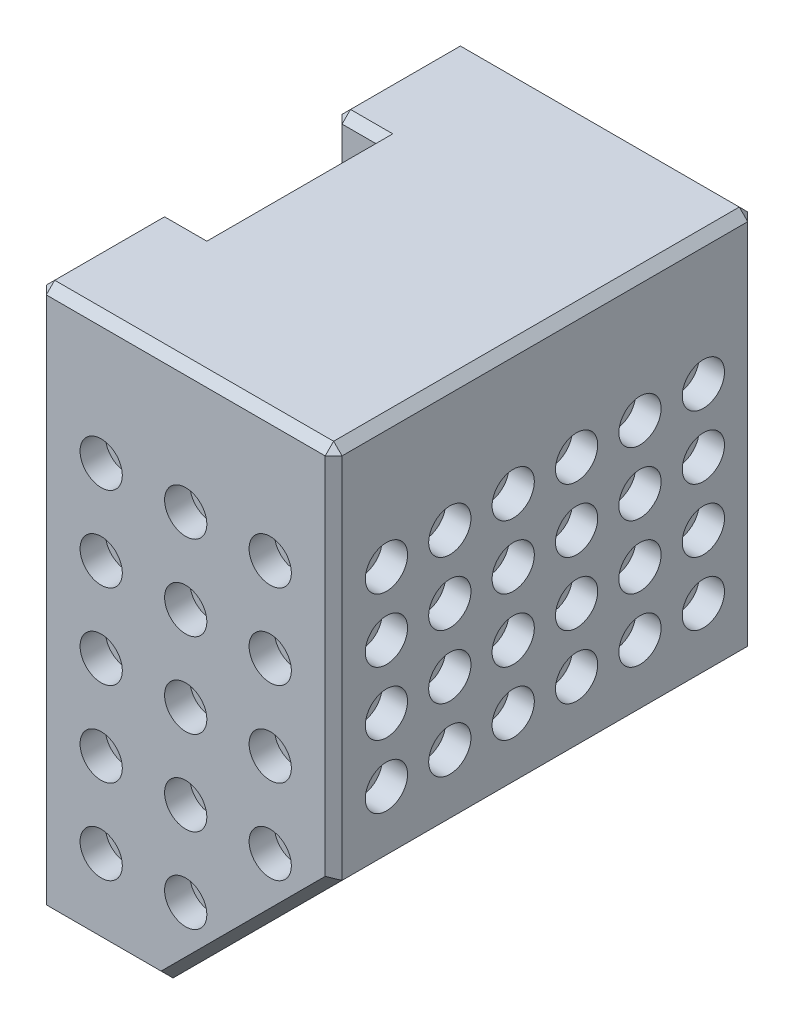
SolidWorks part; units mm, degrees
material "K110"
ref_plane "Front Plane" through (0, 0, 0) normal (0, 0, 1) x (1, 0, 0)
ref_plane "Top Plane" through (0, 0, 0) normal (0, 1, 0) x (1, 0, 0)
ref_plane "Right Plane" through (0, 0, 0) normal (1, 0, 0) x (0, 0, -1)
sketch "Sketch1" plane through (0, 0, 0) normal (0, 1, 0) x (1, 0, 0)
  line L1 (-17.5, -25) -> (17.5, -25)
  line L2 (-17.5, -25) -> (-17.5, 25)
  line L3 (-17.5, 25) -> (17.5, 25)
  line L4 (17.5, -25) -> (17.5, 25)
  line L5 (-17.5, -25) -> (17.5, 25) construction
  line L6 (-17.5, 25) -> (17.5, -25) construction
  point P0 (0, 0)
  dimension "D1" = 50
  dimension "D2" = 35
extrude "Boss-Extrude1" add sketch "Sketch1" against normal blind 64.5
sketch "Sketch2" plane through (0, 0, 25) normal (0, 0, 1) x (1, 0, 0)
  line L0 (-2.5, -64.5) -> (17.5, -44.5)
  line L1 (-17.5, -64.5) -> (17.5, -64.5) construction
  line L2 (17.5, -64.5) -> (17.5, 0) construction
  line L3 (17.5, -44.5) -> (17.5, -64.5)
  line L4 (17.5, -64.5) -> (-2.5, -64.5)
  dimension "D1" = 20
  dimension "D2" = 45
extrude "Cut-Extrude1" cut sketch "Sketch2" against normal up to next
sketch "Sketch3" plane through (-17.5, 0, 0) normal (-1, 0, 0) x (0, 0, 1)
  line L0 (-25, -64.5) -> (25, -64.5) construction
  line L1 (-7, -64.5) -> (7, -64.5)
  line L2 (-7, -64.5) -> (-7, -44.5)
  line L3 (-7, -44.5) -> (7, -44.5)
  line L4 (7, -64.5) -> (7, -44.5)
  line L5 (-25, -44.5) -> (25, -44.5) construction
  point P8 (0, -44.5)
  dimension "D1" = 14
  dimension "D2" = 20
extrude "Cut-Extrude2" cut sketch "Sketch3" against normal up to next
fillet "Fillet1" 2 edges at (0, -44.5, -7) (0, -44.5, 7) type full round first side face at (-5, -54.5, -7) second side face at (-5, -54.5, 7) middle face at (0, -44.5, 0)
sketch "Sketch4" plane through (0, 0, 0) normal (0, 1, 0) x (1, 0, 0)
  line L0 (-17.5, 0) -> (17.5, 0) construction
  line L1 (-17.5, 25) -> (-17.5, -25) construction
  line L2 (17.5, -25) -> (17.5, 25) construction
  line L4 (-17.5, -10) -> (-12.5, -10)
  line L5 (-17.5, -10) -> (-17.5, 10)
  line L6 (-17.5, 10) -> (-12.5, 10)
  line L7 (-12.5, -10) -> (-12.5, 10)
  dimension "D1" = 5
  dimension "D2" = 20
extrude "Cut-Extrude3" cut sketch "Sketch4" against normal blind 43
sketch "Sketch5" plane through (-17.5, 0, 0) normal (-1, 0, 0) x (0, 0, 1)
  line L0 (-10, -43) -> (-10, 0) construction
  line L1 (-15, -43) -> (15, -43)
  line L2 (-15, -43) -> (-15, -38)
  line L3 (-15, -38) -> (15, -38)
  line L4 (15, -43) -> (15, -38)
  line L5 (-10, -43) -> (10, -43) construction
  line L6 (10, -43) -> (10, 0) construction
  dimension "D1" = 5
  dimension "D2" = 5
  dimension "D3" = 5
extrude "Cut-Extrude4" cut sketch "Sketch5" against normal up to surface (5 mm away) up to face at (-12.5, -21.5, 0)
fillet "Fillet5" 2 edges at (-15, -43, -15) (-15, -38, -15) type full round first side face at (-15, -43, 0) second side face at (-15, -38, -12.5) middle face at (-15, -40.5, -15)
fillet "Fillet6" 2 edges at (-15, -43, 15) (-15, -38, 15) type full round first side face at (-15, -43, 1.25) second side face at (-15, -38, 12.5) middle face at (-15, -40.5, 15)
chamfer "Chamfer1" distance 1 angle 45 28 edges at (-17.5, -38, 11.25) (-17.5, -19, 10) (-17.5, -64.5, 16) (-17.5, -58, 7) (-17.5, -44.5, 0) (-17.5, -58, -7) (-17.5, -64.5, -16) (-17.5, -40.5, 15) (-17.5, -43, 0) (-17.5, -40.5, -15) (-17.5, -38, -11.25) (-17.5, -19, -10) (17.5, 0, 0) (17.5, -22.25, -25) (0, 0, -25) (7.5, -54.5, -25) (-10, -64.5, -25) (-17.5, -32.25, -25) (-17.5, 0, -17.5) (-15, 0, -10) (-12.5, 0, 0) (-15, 0, 10) (-17.5, 0, 17.5) (-10, -64.5, 25) (-17.5, -32.25, 25) (0, 0, 25) (17.5, -22.25, 25) (7.5, -54.5, 25)
sketch "Sketch6" plane through (0, 0, 25) normal (0, 0, 1) x (1, 0, 0)
  line L0 (-16.5, 0) -> (16.5, 0) construction
  line L1 (-17.5, -63.5) -> (-17.5, -1) construction
  circle A0 centre (-10, -15) radius 2.5
  point P6 (0, 0)
  point P10 (0, 0)
  dimension "D1" = 5
  dimension "D2" = 15
  dimension "D3" = 7.5
extrude "Cut-Extrude5" cut sketch "Sketch6" against normal blind 3
pattern_linear "LPattern1" count 3 spacing 10 along (1, 0, 0) count 5 spacing 10 along (0, -1, 0) skipping (2, 4) of "Cut-Extrude5"
sketch "Sketch9" plane through (17.5, 0, 0) normal (1, 0, 0) x (0, 0, -1)
  line L0 (-25, -44.0858) -> (-25, -1) construction
  line L1 (-24, 0) -> (24, 0) construction
  circle A0 centre (-18.75, -15) radius 2.5
  dimension "D1" = 5
  dimension "D2" = 6.25
  dimension "D3" = 15
extrude "Cut-Extrude20" cut sketch "Sketch9" against normal blind 3
pattern_linear "LPattern2" count 4 spacing 7.5 along (0, -1, 0) count 6 spacing 7.5 along (0, 0, -1) of "Cut-Extrude20"
sketch "Sketch10" plane through (-17.5, 0, 0) normal (-1, 0, 0) x (0, 0, 1)
  line L0 (-11, -1) -> (-24, -1) construction
  line L2 (-24, 0) -> (-11, 0) construction
  circle A0 centre (-17.5, -15) radius 2.5
  point P4 (0, 0)
  point P7 (-17.5, -1)
  point P8 (0, 0)
  dimension "D1" = 5
  dimension "D2" = 15
extrude "Cut-Extrude21" cut sketch "Sketch10" against normal blind 3
pattern_linear "LPattern3" count 7 spacing 7.5 along (0, -1, 0) count 2 spacing 35 along (0, 0, 1) of "Cut-Extrude21"
sketch "Sketch11" plane through (31, -31, 0) normal (0.7071, -0.7071, 0) x (0, 0, -1)
  line L0 (-25, -46.9619) -> (-25, -19.5061) construction
  line L2 (0, -19.0919) -> (-24, -19.0919) construction
  circle A0 centre (-18.75, -26.5919) radius 2.5
  point P30 (0, 0)
  point P31 (0, 0)
  point P32 (0, 0)
  point P33 (0, 0)
  point P34 (0, 0)
  point P35 (0, 0)
  dimension "D1" = 6.25
  dimension "D2" = 5
  dimension "D5" = 7.5
extrude "Cut-Extrude23" cut sketch "Sketch11" against normal blind 3
pattern_linear "LPattern5" count 6 spacing 7.5 along (0, 0, -1) count 3 spacing 7.5 along (-0.7071, -0.7071, 0) skipping (2, 0), (2, 1), (2, 2), (3, 0), (3, 1), (3, 2) of "Cut-Extrude23"
sketch "Sketch18" plane through (0, 0, -25) normal (0, 0, -1) x (-1, 0, 0)
  circle A0 centre (10, -15) radius 2.5
extrude "Cut-Extrude25" cut sketch "Sketch18" against normal blind 3
pattern_linear "LPattern7" count 3 spacing 10 along (1, 0, 0) count 5 spacing 10 along (0, -1, 0) of "Cut-Extrude25"
